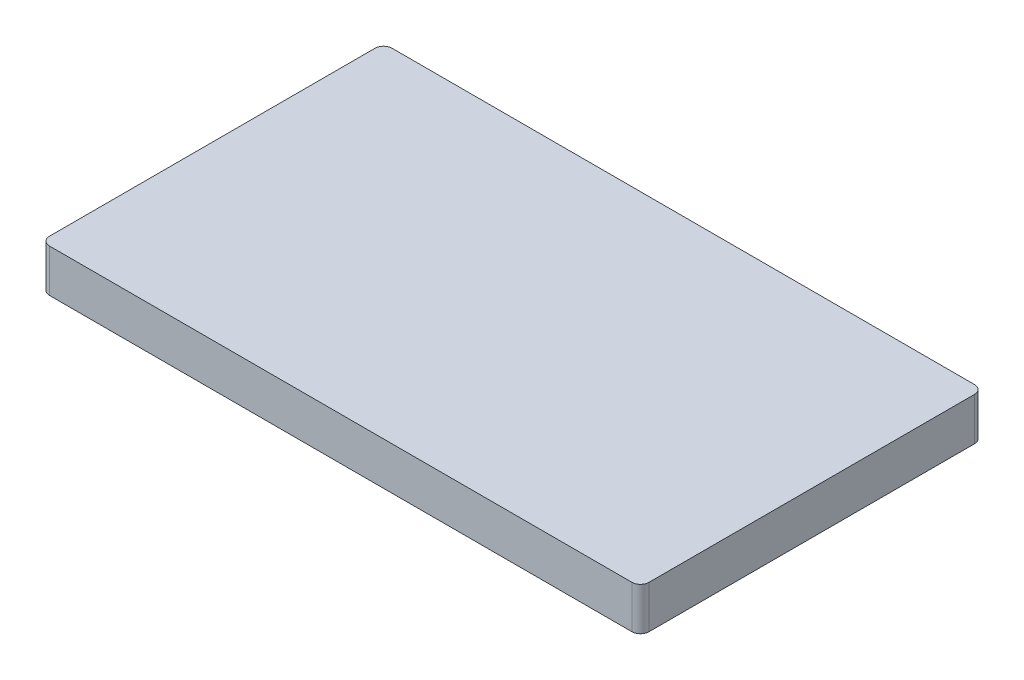
SolidWorks part; units mm, degrees
ref_plane "Front Plane" through (0, 0, 0) normal (0, 0, 1) x (1, 0, 0)
ref_plane "Top Plane" through (0, 0, 0) normal (0, 1, 0) x (1, 0, 0)
ref_plane "Right Plane" through (0, 0, 0) normal (1, 0, 0) x (0, 0, -1)
sketch "Sketch1" plane through (0, 0, 0) normal (0, 1, 0) x (1, 0, 0)
  line L1 (-70, -40) -> (70, -40)
  line L2 (-70, -40) -> (-70, 40)
  line L3 (-70, 40) -> (70, 40)
  line L4 (70, -40) -> (70, 40)
  line L5 (-70, -40) -> (70, 40) construction
  line L6 (-70, 40) -> (70, -40) construction
  point P0 (0, 0)
  dimension "D1" = 140
  dimension "D2" = 80
extrude "Boss-Extrude1" add sketch "Sketch1" along normal blind 10
fillet "Fillet1" radius 2 4 edges at (-70, 5, -40) (70, 5, -40) (70, 5, 40) (-70, 5, 40)
